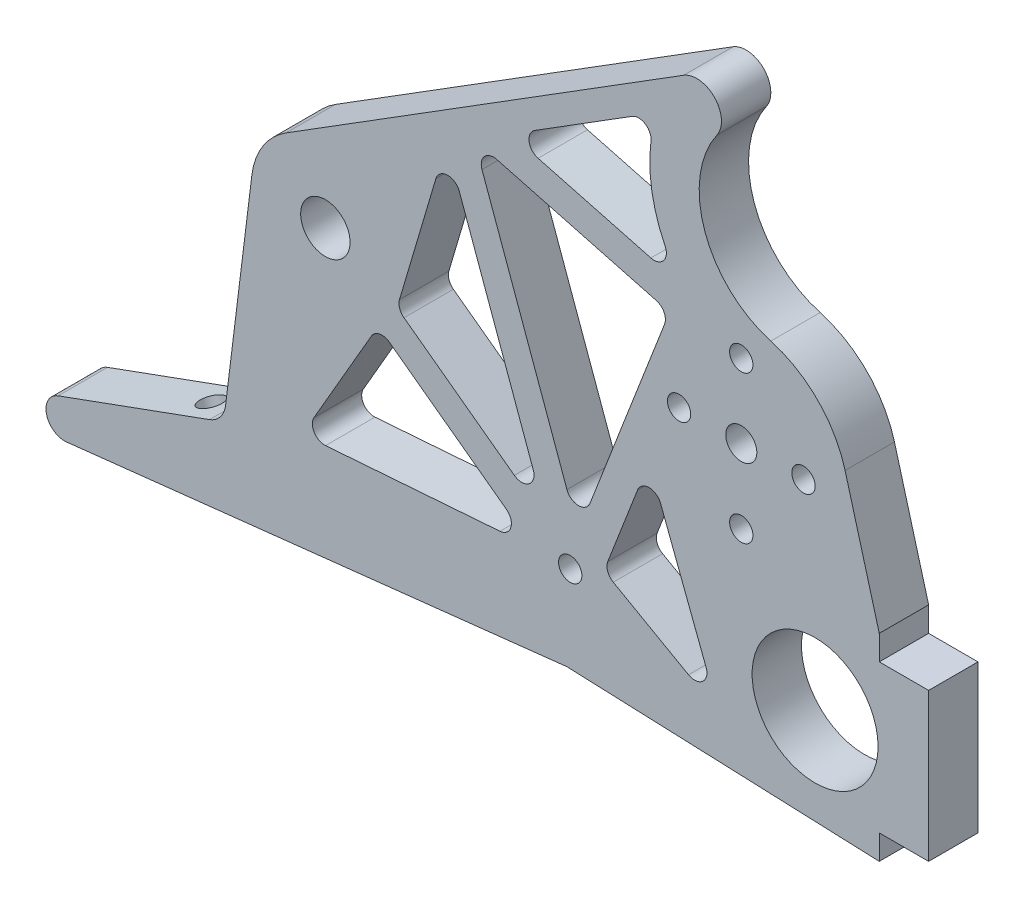
SolidWorks part; units mm, degrees
ref_plane "Front Plane" through (0, 0, 0) normal (0, 0, 1) x (1, 0, 0)
ref_plane "Top Plane" through (0, 0, 0) normal (0, 1, 0) x (1, 0, 0)
ref_plane "Right Plane" through (0, 0, 0) normal (1, 0, 0) x (0, 0, -1)
sketch "Sketch1" plane through (0, 0, 0) normal (0, 0, 1) x (1, 0, 0)
  line L0 (14.5951, 62.2929) -> (-36.5475, 30.3002)
  line L1 (0, -3.4925) -> (0, 3.4925) construction
  line L2 (39.751, 9.525) -> (46.101, 9.525)
  line L3 (39.751, 9.525) -> (39.751, -9.525) construction
  line L4 (39.751, -9.525) -> (46.101, -9.525)
  line L5 (46.101, 9.525) -> (46.101, -9.525)
  line L6 (14.0023, 24.9685) -> (30.0023, 24.9685) construction
  line L7 (22.0023, 34.4685) -> (22.0023, 15.4685) construction
  line L8 (39.751, 9.525) -> (39.751, 12.7)
  line L9 (39.751, -9.525) -> (39.751, -12.7)
  line L10 (-37.3035, 14.6753) -> (-6.7754, -8.808)
  line L11 (39.751, -12.7) -> (-0.441, -11.1037)
  line L12 (-11.2218, 115.1427) -> (23226.9166, -41331.4577) construction
  line L14 (22.0023, 24.9685) -> (35.1908, 32.363) construction
  line L15 (39.751, 12.7) -> (35.3543, 28.6493)
  line L16 (22.0023, 24.9685) -> (24.7256, 17.8063)
  line L17 (24.7256, 17.8063) -> (26.9246, 12.0227) construction
  line L18 (26.9246, 12.0227) -> (28.6172, 7.5712)
  line L19 (28.6172, 7.5712) -> (31.496, 0) construction
  circle A2 centre (31.496, 0) radius 19.05 construction
  circle A3 centre (-31.496, 0) radius 19.05 construction
  circle A4 centre (-31.496, 22.225) radius 38.1 construction
  circle A5 centre (0, 0) radius 1.5
  circle A6 centre (22.0023, 34.4685) radius 1.5
  circle A7 centre (30.0023, 24.9685) radius 1.5
  circle A8 centre (22.0023, 15.4685) radius 1.5
  circle A9 centre (14.0023, 24.9685) radius 1.5
  circle A11 centre (-31.496, 22.225) radius 3.175
  arc A12 (-36.5475, 30.3002) -> (-37.3035, 14.6753) centre (-31.496, 22.225) ccw
  arc A19 (35.3543, 28.6493) -> (25.8019, 38.2871) centre (22.0023, 24.9685) ccw
  arc A20 (18.8804, 57.7809) -> (14.5951, 62.2929) centre (16.279, 59.6012) ccw
  arc A21 (-6.7754, -8.808) -> (-0.441, -11.1037) centre (0, 0) ccw
  arc A22 (18.8804, 57.7809) -> (25.8019, 38.2871) centre (29.286, 50.4999) ccw
  arc A23 (-37.3035, 14.6753) -> (-36.5475, 30.3002) centre (-31.496, 22.225) ccw construction
  circle A31 centre (22.0023, 24.9685) radius 2
  arc A33 (4.6247, 10.1045) -> (-6.7754, -8.808) centre (0, 0) ccw construction
  arc A34 (-0.441, -11.1037) -> (4.6247, 10.1045) centre (0, 0) ccw construction
  arc A35 (25.8019, 38.2871) -> (16.8069, 12.1299) centre (22.0023, 24.9685) ccw construction
  arc A36 (16.8069, 12.1299) -> (35.3543, 28.6493) centre (22.0023, 24.9685) ccw construction
  circle A37 centre (31.496, 0) radius 8.1
  point P2 (34.083, 31.7419)
  point P10 (46.101, 0)
  point P13 (-31.496, -19.05)
  point P24 (-31.496, -15.875)
  point P26 (22.0023, 24.9685)
  point P29 (22.0023, 24.9685)
  point P37 (42.926, -9.525)
  dimension "D7" = 38.1
  dimension "D8" = 76.2
  dimension "D11" = 3
  dimension "D13" = 3
  dimension "D14" = 27.7
  dimension "D16" = 6.35
  dimension "D17" = 19.05
  dimension "D21" = 6.35
  dimension "D22" = 1.27
  dimension "D23" = 16.2
  dimension "D25" = 12.7
  dimension "D26" = 4
  dimension "D19" = 22.225
  dimension "D24" = 60.325
  dimension "D3" = 19.05
  dimension "D4" = 6.35
  dimension "D5" = 11.43
  dimension "D6" = 62.992
  dimension "D9" = 3.175
  dimension "D10" = 19
  dimension "D12" = 16
  dimension "D15" = 4.7625
  dimension "D18" = 53.5686
  dimension "D20" = 3.175
extrude "Boss-Extrude1" add sketch "Sketch1" along normal mid plane 6.35 contours L10 L11 L9 L4 L5 L2 L8 A12 A20 A6 A7 A8 A9 A11 region at (3.9495, 19.6895, 0)
sketch "Sketch2" plane through (0, 0, 3.175) normal (0, 0, 1) x (1, 0, 0)
  line L0 (-46.398, -6.562) -> (-65.8615, -13.6461) construction
  line L1 (-46.398, -6.562) -> (-65.8615, -13.6461)
  line L2 (-44.3329, -3.9682) -> (-40.949, 23.3941)
  line L3 (-64.7842, -18.2505) -> (-0.441, -11.1037)
  line L4 (-37.3035, 14.6753) -> (-6.7754, -8.808) construction
  line L5 (-37.3035, 14.6753) -> (-6.7754, -8.808)
  arc A0 (-65.8615, -13.6461) -> (-64.8428, -18.2563) centre (-65.0471, -15.8838) ccw construction
  arc A1 (-65.8615, -13.6461) -> (-64.7842, -18.2505) centre (-65.0471, -15.8838) ccw
  arc A2 (-6.7754, -8.808) -> (-0.441, -11.1037) centre (0, 0) ccw construction
  arc A3 (-46.398, -6.562) -> (-44.3329, -3.9682) centre (-47.4839, -3.5785) ccw
  arc A4 (-36.5475, 30.3002) -> (-37.3035, 14.6753) centre (-31.496, 22.225) ccw construction
  arc A5 (-6.7754, -8.808) -> (-0.441, -11.1037) centre (0, 0) ccw
  arc A6 (-40.949, 23.3941) -> (-37.3035, 14.6753) centre (-31.496, 22.225) ccw
  dimension "D1" = 3.175
extrude "Boss-Extrude2" add sketch "Sketch2" against normal up to surface (6.35 mm away) up to face at (39.596, 0, -3.175)
sketch "Sketch3" plane through (-3.3185, 9.1176, 0) normal (-0.342, 0.9397, 0) x (0.9397, 0.342, 0)
  line L0 (-45.8442, 3.175) -> (-45.8442, -3.175) construction
  line L1 (-49.0192, 0) -> (-45.8442, 0) construction
  circle A0 centre (-49.0192, 0) radius 1.5
  dimension "D1" = 3
  dimension "D2" = 3.175
extrude "Cut-Extrude1" cut sketch "Sketch3" against normal blind 6
sketch "Sketch4" plane through (0, 0, -3.175) normal (0, 0, -1) x (-1, 0, 0)
  line L0 (-11.1755, 56.4087) -> (7.6665, 44.6219)
  line L1 (12.3845, 41.6705) -> (-1.0195, 4.6521)
  line L2 (2.9671, 3.7253) -> (15.9085, 39.466)
  line L4 (-12.7769, 34.9844) -> (-1.0195, 4.6521)
  line L8 (-31.496, 0) -> (-19.0526, -6.35) construction
  line L9 (-14.5951, 62.2929) -> (36.5475, 30.3002) construction
  line L10 (-14.5951, 62.2929) -> (36.5475, 30.3002)
  line L11 (-11.1755, 56.4087) -> (-9.4917, 59.1004) construction
  line L12 (-10.151, 16.9655) -> (-19.0526, -6.35)
  line L13 (15.9085, 39.466) -> (22.2768, 17.9552)
  line L14 (2.9671, 3.7253) -> (22.2768, 17.9552)
  line L15 (24.6877, 14.6836) -> (4.7625, 0)
  line L16 (4.251, 2.1472) -> (31.496, 22.225) construction
  line L17 (15.101, 7.6188) -> (12.69, 10.8904) construction
  line L18 (4.7625, 0) -> (34.4639, -2.2183)
  line L20 (12.3845, 41.6705) -> (-12.7769, 34.9844)
  line L21 (-14.2547, 38.7968) -> (7.6665, 44.6219)
  line L22 (-3.2941, 41.7093) -> (-2.2504, 37.7816) construction
  line L23 (7.6665, 44.6219) -> (12.3845, 41.6705) construction
  line L25 (9.5037, 21.7777) -> (5.6825, 23.1613) construction
  line L26 (-14.2547, 38.7968) -> (-12.7769, 34.9844) construction
  line L28 (24.6877, 14.6836) -> (34.4639, -2.2183)
  line L29 (-10.5206, 47.2191) -> (-16.7757, 48.3127) construction
  line L31 (46.398, -6.562) -> (34.4639, -2.2183) construction
  line L32 (65.8615, -13.6461) -> (46.398, -6.562) construction
  line L33 (-19.0526, -6.35) -> (-4.3373, 1.967)
  line L34 (-4.3373, 1.967) -> (-10.151, 16.9655)
  line L35 (-3.9195, 12.1338) -> (-7.7088, 10.665) construction
  line L36 (-39.751, -12.7) -> (0.441, -11.1037) construction
  arc A1 (-14.2547, 38.7968) -> (-11.1755, 56.4087) centre (-29.286, 50.4999) ccw
  arc A2 (-25.8019, 38.2871) -> (-18.8804, 57.7809) centre (-29.286, 50.4999) ccw construction
  circle A3 centre (-31.496, 0) radius 8.1 construction
  circle A4 centre (-31.496, 0) radius 8.1
  circle A5 centre (0, 0) radius 4.7625 construction
  arc A6 (23.317, 16.1976) -> (24.6877, 14.6836) centre (31.496, 22.225) ccw construction
  arc A7 (22.2768, 17.9552) -> (23.317, 16.1976) centre (31.496, 22.225) ccw construction
  circle A8 centre (-14.0023, 24.9685) radius 1.5 construction
  point P34 (13.8955, 9.2546)
  point P46 (3.9213, -2.2183)
  point P47 (4.2914, 0)
  point P48 (40.4309, -4.3902)
  point P49 (4.2914, 0)
  point P50 (34.4639, -2.2183)
  point P53 (4.7625, 0)
  dimension "D5" = 9.525
  dimension "D11" = 8.8815
  dimension "D1" = 6.35
  dimension "D2" = 4.064
  dimension "D3" = 10.16
  dimension "D4" = 4.7625
  dimension "D6" = 3.175
  dimension "D7" = 12.7
  dimension "D8" = 22.225
  dimension "D9" = 13.97
  dimension "D10" = 5.5236
  dimension "D12" = 29.7841
extrude "Cut-Extrude2" cut sketch "Sketch4" against normal through all and the other way through all contours A1 L21 L0 | L1 L20 L4 | L2 L14 | L15 | L33 L34 L12 region at (4.9103, 46.4656, -3.175) region at (0.4706, 27.1024, -3.175) region at (-13.7175, 20.3822, -3.175) region at (11.1803, 4.1942, -3.175) region at (-21.3047, 4.1551, -3.175)
fillet "Fillet1" radius 1.5875 15 edges at (-7.6665, 44.6219, 0) (11.1755, 56.4087, 0) (12.7769, 34.9844, 0) (-12.3845, 41.6705, 0) (-22.2768, 17.9552, 0) (-15.9085, 39.466, 0) (-24.6877, 14.6836, 0) (-2.9671, 3.7253, 0) (1.0195, 4.6521, 0) (14.2547, 38.7968, 0) (4.3373, 1.967, 0) (10.151, 16.9655, 0) (19.0526, -6.35, 0) (-34.4639, -2.2183, 0) (-4.7625, 0, 0)
sketch "Sketch7" plane through (-0.441, -11.1037, 0) normal (-0.0397, -0.9992, 0) x (0.9992, -0.0397, 0)
  line L0 (6.35, -3.175) -> (6.35, 3.175) construction
  line L1 (40.2237, 3.175) -> (0, 3.175) construction
  line L2 (40.2237, -3.175) -> (0, -3.175) construction
  line L4 (6.35, 0) -> (19.05, 0) construction
  line L5 (0, 3.175) -> (0, -3.175) construction
  circle A0 centre (6.35, 0) radius 1.5
  circle A1 centre (19.05, 0) radius 1.5
  point P9 (6.35, 0)
  dimension "D1" = 12.7
  dimension "D2" = 3
  dimension "D3" = 6.35
extrude "Cut-Extrude4" cut sketch "Sketch7" against normal blind 6
